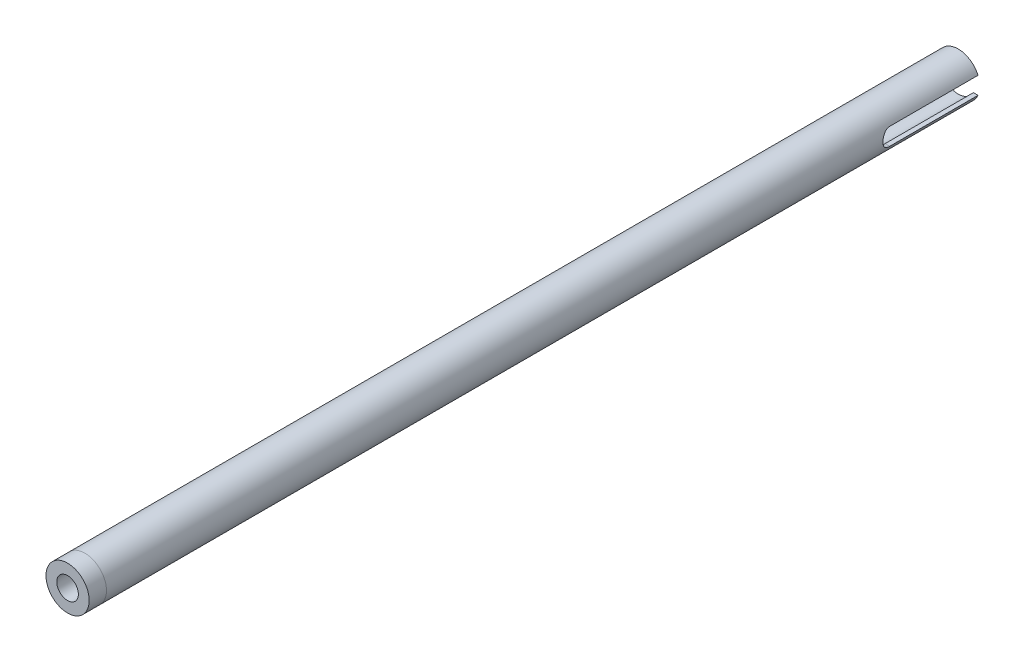
SolidWorks part; units mm, degrees
material "AISI 4130 Steel, annealed at 865C"
ref_plane "Front Plane" through (0, 0, 0) normal (0, 0, 1) x (1, 0, 0)
ref_plane "Top Plane" through (0, 0, 0) normal (0, 1, 0) x (1, 0, 0)
ref_plane "Right Plane" through (0, 0, 0) normal (1, 0, 0) x (0, 0, -1)
sketch "Axis" plane through (0, 0, 0) normal (0, 1, 0) x (1, 0, 0)
  line L0 (0, 0) -> (0, 326.9591) construction
  line L1 (0, 0) -> (0, -28.575) construction
  line L2 (0, 326.9591) -> (-7.9375, 326.9591) construction
  line L4 (0, 355.931) -> (-25.9803, 261.103) construction
  dimension "D1" = 28.575
  dimension "D2" = 7.9375
sketch "Sketch1" plane through (0, 0, 0) normal (0, 0, 1) x (1, 0, 0)
  line L0 (-7.9375, 0) -> (7.9375, 0) construction
  line L1 (-7.2748, 3.175) -> (7.2748, 3.175)
  line L2 (-7.2748, -3.175) -> (7.2748, -3.175)
  circle A0 centre (0, 0) radius 7.9375
  circle A1 centre (0, 0) radius 6.4135
  circle A2 centre (0, 0) radius 3.9688
  dimension "D1" = 15.875
  dimension "D3" = 7.9375
  dimension "D2" = 1.524
  dimension "D4" = 6.35
extrude "Threaded insert 1-1" add sketch "Sketch1" against normal blind 6.35 contours A2 L1 A1 | A1 L1 A0 | A2 L0 A1 L1 | A1 L0 A0 L1 | L0 A1 L2 A0 | L0 A2 L2 A1 | A2 L2 A1 | A1 L2 A0 | L0 A1 L2 A2 | L0 A0 L2 A1 | A0 L0 A1 L1 | A1 L0 A2 L1 region at (4.7887, 1.6543, 0) region at (4.7887, -1.6543, 0) region at (6.9234, 1.6163, 0) region at (6.9234, -1.6163, 0) region at (-4.7887, -1.6543, 0) region at (-4.7887, 1.6543, 0) region at (0, 4.6159, 0) region at (0, -4.6159, 0) region at (0, 6.5666, 0) region at (6.4237, -3.3281, 0) region at (-6.9234, -1.6163, 0) region at (-6.9234, 1.6163, 0)
extrude "Threaded insert 1-2" add sketch "Sketch1<3>" against normal blind 9.525 from surface contours A2 L1 A1 | A2 L0 A1 L1 | L0 A2 L2 A1 | A2 L2 A1 | L0 A1 L2 A2 | A1 L0 A2 L1 region at (4.7887, 1.6543, 0) region at (4.7887, -1.6543, 0) region at (-4.7887, -1.6543, 0) region at (-4.7887, 1.6543, 0) region at (0, 4.6159, 0) region at (0, -4.6159, 0) starting at face at (7.9375, 0, -6.35)
sketch "Sketch1<3>" plane through (0, 0, 0) normal (0, 0, 1) x (1, 0, 0) same geometry as "Sketch1"
extrude "A-arm tube" add sketch "Sketch1<4>" against normal up to vertex (326.9591 mm away) from surface separate body contours A1 L1 A0 | A1 L0 A0 L1 | L0 A1 L2 A0 | A1 L2 A0 | L0 A0 L2 A1 | A0 L0 A1 L1 region at (6.9234, 1.6163, 0) region at (6.9234, -1.6163, 0) region at (0, 6.5666, 0) region at (6.4237, -3.3281, 0) region at (-6.9234, -1.6163, 0) region at (-6.9234, 1.6163, 0) up to point (0, 0, -326.9591) starting at face at (6.4135, 0, -6.35)
sketch "Sketch1<4>" plane through (0, 0, 0) normal (0, 0, 1) x (1, 0, 0) same geometry as "Sketch1"
extrude "Apex slot" cut sketch "Sketch1<5>" along normal blind 35.56 from surface contours A0 L0 A1 L1 | L0 A0 L2 A1 | A1 L0 A0 L1 | L0 A1 L2 A0 region at (6.9234, 1.6163, 0) region at (6.9234, -1.6163, 0) region at (-6.9234, -1.6163, 0) region at (-6.9234, 1.6163, 0) starting at face at (6.4135, 0, -326.9591)
sketch "Sketch1<5>" plane through (0, 0, 0) normal (0, 0, 1) x (1, 0, 0) same geometry as "Sketch1"
fillet "Fillet1" radius 3.175 4 edges at (-6.4237, 3.175, -291.3991) (-6.4237, -3.175, -291.3991) (6.4237, -3.175, -291.3991) (6.4237, 3.175, -291.3991)
equation "\"tube diameter\"= 5 / 8"
equation "\"tube thickness\"= .06"
equation "\"apex thickness\"= .25"
equation "\"tube slot\"= 1.4"
equation "\"D1@Sketch1\"=\"tube diameter\""
equation "\"D2@Sketch1\"=\"tube thickness\""
equation "\"threaded insert hole\"= .3125"
equation "\"D3@Sketch1\"=\"threaded insert hole\""
equation "\"D4@Sketch1\"=\"apex thickness\""
equation "\"D1@Apex slot\" = \"tube slot\""
equation "\"D1@Fillet1\"=\"apex thickness\"/2"
equation "\"D2@Axis\"=\"tube diameter\"/2"
